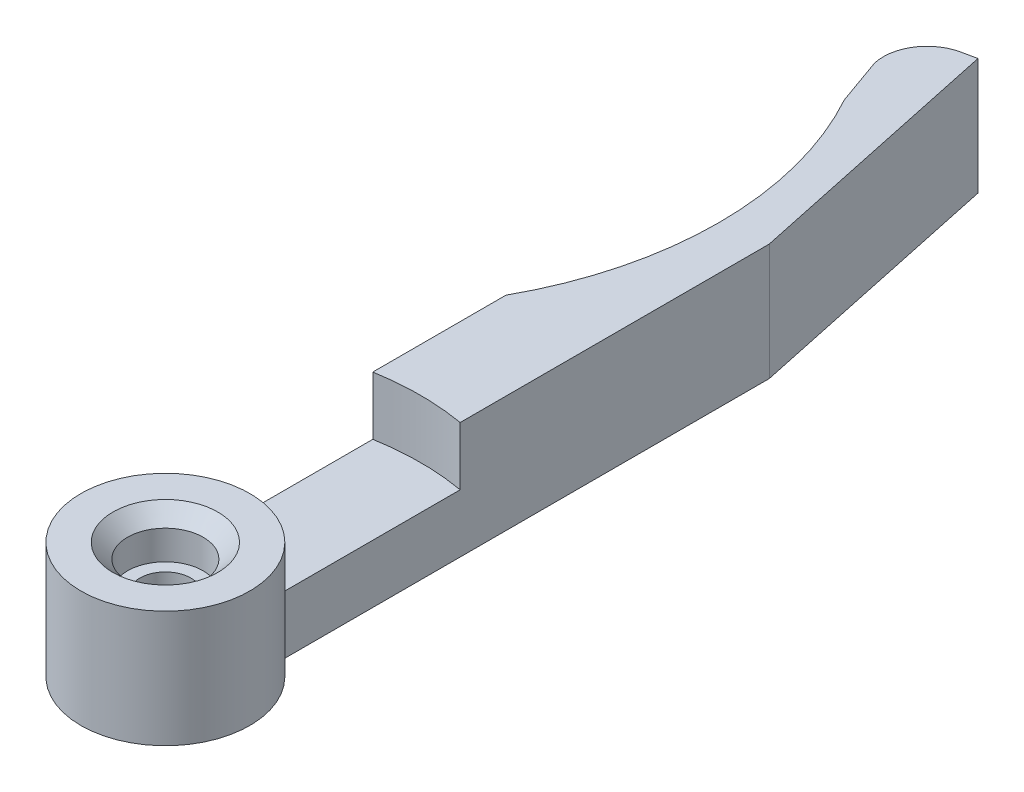
SolidWorks part; units mm, degrees
ref_plane "Plan de face" through (0, 0, 0) normal (0, 0, 1) x (1, 0, 0)
ref_plane "Plan de dessus" through (0, 0, 0) normal (0, 1, 0) x (1, 0, 0)
ref_plane "Plan de droite" through (0, 0, 0) normal (1, 0, 0) x (0, 0, -1)
sketch "Esquisse1" plane through (0, 0, 0) normal (0, 1, 0) x (1, 0, 0)
  line L0 (-3, 50.619) -> (-3, 49.619) construction
  line L1 (2, 55.619) -> (3, 55.619) construction
  line L2 (-3, 55.619) -> (-3, 4.9639) construction
  line L3 (-3, 4.9639) -> (3, 4.9639) construction
  line L4 (3, 55.619) -> (3, 4.9639) construction
  line L5 (-3, 26.381) -> (-3, 4.9639)
  line L7 (-3, 4.9639) -> (3, 4.9639) construction
  line L12 (0, 4.9639) -> (0, -14.5149) construction
  line L13 (-4.1404, 52.822) -> (-3, 49.619)
  line L14 (-1.8453, 56.4495) -> (-0.8672, 56.6574)
  line L15 (-0.8672, 56.6574) -> (3, 38.4639)
  line L16 (3, 38.4639) -> (3, 4.9639)
  arc A0 (-3, 49.619) -> (-3, 26.381) centre (-24, 38) cw
  arc A1 (2, 55.619) -> (-3, 50.619) centre (2, 50.619) ccw construction
  circle A2 centre (0, 0) radius 2.4 construction
  arc A3 (-4.1404, 52.822) -> (-1.8453, 56.4495) centre (-1.2216, 53.5151) cw
  arc A4 (-3, 4.9639) -> (3, 4.9639) centre (0, 0) ccw
  point P19 (0, 38)
  point P25 (-4.3024, 55.9871)
  dimension "D2" = 24
  dimension "D5" = 5
  dimension "D10" = 3
  dimension "D7" = 4.8
  dimension "D11" = 5.8
  dimension "D1" = 6
  dimension "D3" = 21
  dimension "D4" = 6
  dimension "D6" = 38
  dimension "D8" = 3.5
  dimension "D9" = 6.5
  dimension "D12" = 33.5
  dimension "D13" = 12
  dimension "D14" = 18.6
  dimension "D15" = 3.4
  dimension "D16" = 1
extrude "Boss.-Extru.1" add sketch "Esquisse1" along normal blind 8
sketch "Esquisse2" plane through (0, 8, 0) normal (0, 1, 0) x (1, 0, 0)
  line L0 (0, 38) -> (0, 0) construction
  circle A0 centre (0, 0) radius 2.6
  arc A1 (-3, 26.381) -> (-3, 49.619) centre (-24, 38) ccw construction
  dimension "D2" = 5.2
  dimension "D1" = 38
extrude "Enlèv. mat.-Extru.1" cut sketch "Esquisse2" against normal blind 3
sketch "Esquisse3" plane through (0, 5, 0) normal (0, 1, 0) x (1, 0, 0)
  circle A0 centre (0, 0) radius 1.75
  dimension "D1" = 3.5
extrude "Enlèv. mat.-Extru.2" cut sketch "Esquisse3" against normal up to next
sketch "Esquisse4" plane through (0, 0, 0) normal (0, -1, 0) x (1, 0, 0)
  circle A0 centre (0, 0) radius 3.75
  dimension "D1" = 7.5
extrude "Enlèv. mat.-Extru.3" cut sketch "Esquisse4" against normal blind 2
sketch "Esquisse5" plane through (0, 8, 0) normal (0, 1, 0) x (1, 0, 0)
  line L0 (-3, 4.9639) -> (-3, 17.2409)
  line L1 (3, 4.9639) -> (3, 17.2409)
  line L2 (3, 4.9639) -> (3, 38.4639) construction
  circle A0 centre (0, 0) radius 5.8 construction
  circle A1 centre (0, 0) radius 17.5 construction
  arc A2 (-3, 4.9639) -> (3, 4.9639) centre (0, 0) ccw construction
  arc A3 (-3, 4.9639) -> (3, 4.9639) centre (0, 0) cw
  arc A4 (-3, 17.2409) -> (3, 17.2409) centre (0, 0) cw
  dimension "D1" = 35
extrude "Enlèv. mat.-Extru.4" cut sketch "Esquisse5" against normal blind 4
chamfer "Chanfrein1" distance 1 angle 45 1 edges at (0, 8, 2.6)
